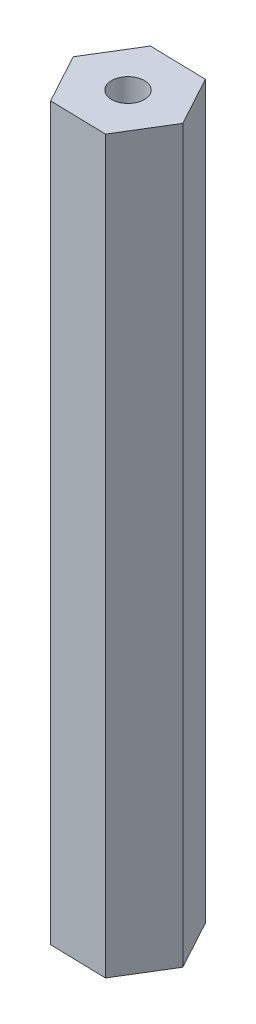
SolidWorks part; units mm, degrees
ref_plane "정면" through (0, 0, 0) normal (0, 0, 1) x (1, 0, 0)
ref_plane "윗면" through (0, 0, 0) normal (0, 1, 0) x (1, 0, 0)
ref_plane "우측면" through (0, 0, 0) normal (1, 0, 0) x (0, 0, -1)
sketch "스케치1" plane through (0, 0, 0) normal (0, 1, 0) x (1, 0, 0)
  line L1 (2.2075, -4.0571) -> (4.6173, -0.1168)
  line L2 (4.6173, -0.1168) -> (2.4098, 3.9403)
  line L3 (2.4098, 3.9403) -> (-2.2075, 4.0571)
  line L4 (-2.2075, 4.0571) -> (-4.6173, 0.1168)
  line L5 (-4.6173, 0.1168) -> (-2.4098, -3.9403)
  line L6 (-2.4098, -3.9403) -> (2.2075, -4.0571)
  circle A0 centre (0, 0) radius 4 construction
  dimension "D1" = 8
extrude "보스-돌출1" add sketch "스케치1" along normal blind 60
sketch "스케치2" plane through (0, 60, 0) normal (0, 1, 0) x (1, 0, 0)
  circle A0 centre (0, 0) radius 1.35
  dimension "D1" = 2.7
extrude "컷-돌출1" cut sketch "스케치2" against normal blind 8
sketch "스케치3" plane through (0, 0, 0) normal (0, -1, 0) x (1, 0, 0)
  circle A0 centre (0, 0) radius 1.35
  dimension "D1" = 2.7
extrude "컷-돌출2" cut sketch "스케치3" against normal blind 8
